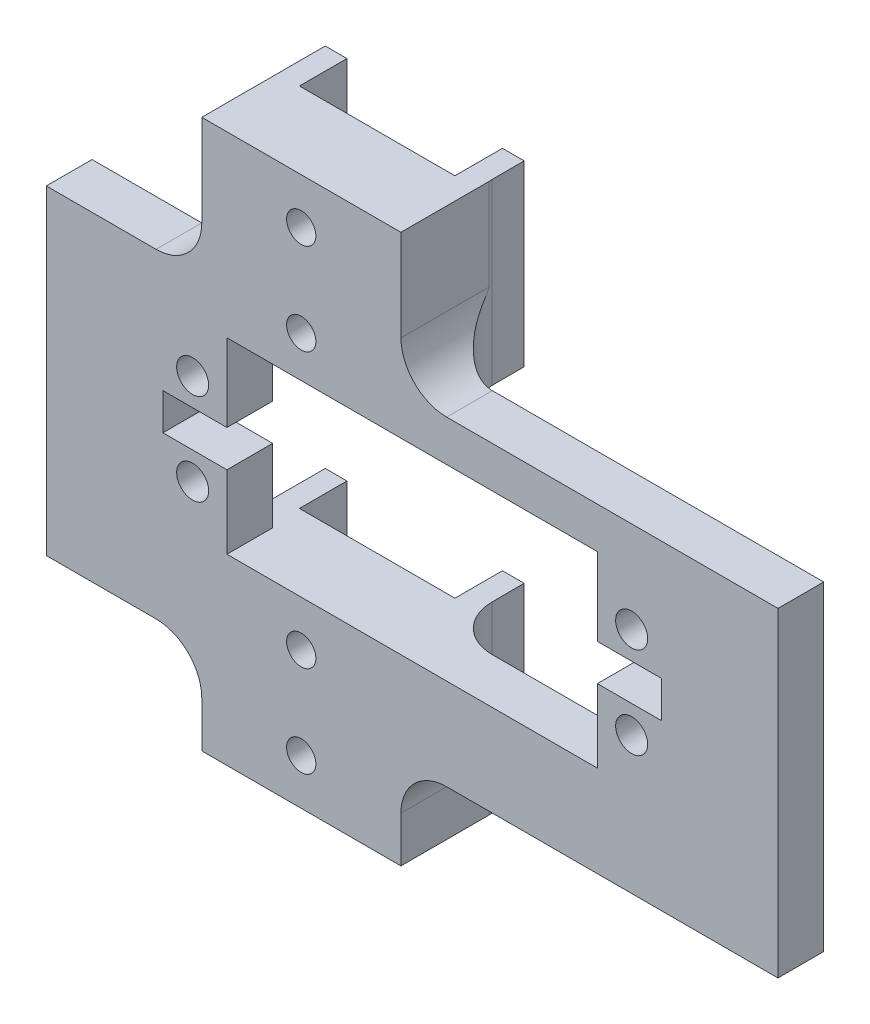
SolidWorks part; units mm, degrees
ref_plane "正面" through (0, 0, 0) normal (0, 0, 1) x (1, 0, 0)
ref_plane "平面" through (0, 0, 0) normal (0, 1, 0) x (1, 0, 0)
ref_plane "右側面" through (0, 0, 0) normal (1, 0, 0) x (0, 0, -1)
sketch "ｽｹｯﾁ1" plane through (0, 0, 0) normal (0, 0, 1) x (1, 0, 0)
  line L0 (-20.25, 10) -> (-20.25, -10)
  line L1 (-24, 5) -> (24, 5) construction
  line L2 (-24, 5) -> (-24, -5) construction
  line L3 (-24, -5) -> (24, -5) construction
  line L4 (24, 5) -> (24, -5) construction
  line L5 (-24, 5) -> (24, -5) construction
  line L6 (-24, -5) -> (24, 5) construction
  line L7 (-29, 10) -> (-20.25, 10)
  line L8 (-29, 10) -> (-29, -20)
  line L9 (-29, -20) -> (29, -20)
  line L10 (29, 10) -> (29, -20)
  line L13 (-20.25, -10) -> (20.25, -10)
  line L14 (20.25, -10) -> (20.25, 10)
  line L16 (0, -12.925) -> (0, 12.925) construction
  line L17 (20.25, 10) -> (29, 10)
  circle A0 centre (-24, 5) radius 1.75
  circle A1 centre (-24, -5) radius 1.75
  circle A2 centre (24, 5) radius 1.75
  circle A3 centre (24, -5) radius 1.75
  point P0 (0, 0)
  point P10 (0, 0)
  dimension "D3" = 3.5
  dimension "D4" = 3.5
  dimension "D5" = 3.5
  dimension "D6" = 3.5
  dimension "D1" = 48
  dimension "D2" = 10
  dimension "D7" = 5
  dimension "D8" = 5
  dimension "D9" = 20.25
  dimension "D10" = 20.25
  dimension "D11" = 20
  dimension "D12" = 30
extrude "ﾎﾞｽ - 押し出し1" add sketch "ｽｹｯﾁ1" along normal blind 5
sketch "ｽｹｯﾁ2" plane through (0, 0, 0) normal (0, 0, -1) x (-1, 0, 0)
  line L0 (20, -10) -> (20, -20)
  line L1 (-20.25, -10) -> (20.25, -10) construction
  line L2 (29, -20) -> (-29, -20) construction
  line L3 (20, -20) -> (23, -20)
  line L4 (23, -20) -> (23, -10)
  line L5 (23, -10) -> (20, -10)
  line L6 (1.25, -10) -> (1.25, -20)
  line L7 (1.25, -20) -> (4.25, -20)
  line L8 (4.25, -20) -> (4.25, -10)
  line L9 (4.25, -10) -> (1.25, -10)
  line L10 (29, 10) -> (29, -20) construction
  dimension "D1" = 6
  dimension "D2" = 3
  dimension "D3" = 3
  dimension "D4" = 15.75
extrude "ﾎﾞｽ - 押し出し2" add sketch "ｽｹｯﾁ2" along normal blind 8.5
sketch "ｽｹｯﾁ3" plane through (0, -10, 0) normal (0, 1, 0) x (1, 0, 0)
  line L0 (-20, 0) -> (-20, 3.3)
  line L1 (-16.5, 0) -> (16.5, 0) construction
  line L2 (-20, 8.5) -> (-20, 0) construction
  line L3 (-20, 3.3) -> (-4.25, 3.3)
  line L4 (-4.25, 8.5) -> (-4.25, 0) construction
  line L5 (-4.25, 3.3) -> (-4.25, 0)
  line L6 (-4.25, 0) -> (-20, 0)
  dimension "D1" = 3.3
extrude "ﾎﾞｽ - 押し出し3" add sketch "ｽｹｯﾁ3" against normal blind 10
sketch "ｽｹｯﾁ4" plane through (0, 0, 0) normal (0, 1, 0) x (1, 0, 0)
  line L0 (-23, 8.5) -> (-23, 0)
  line L1 (-16.5, 0) -> (16.5, 0) construction
  line L2 (-23, 8.5) -> (-23, 0) construction
  line L3 (-23, 0) -> (-1.2236, 0)
  line L4 (-1.2236, 0) -> (-1.25, 8.5)
  line L5 (-1.25, 8.5) -> (-4.25, 8.5)
  line L6 (-4.25, 8.5) -> (-4.25, 3.3)
  line L7 (-4.25, 3.3) -> (-20, 3.3)
  line L8 (-20, 3.3) -> (-20, 8.5)
  line L9 (-20, 8.5) -> (-23, 8.5)
extrude "ﾎﾞｽ - 押し出し4" add sketch "ｽｹｯﾁ4" along normal mid plane 60
sketch "ｽｹｯﾁ6" plane through (0, 0, 0) normal (0, 0, 1) x (1, 0, 0)
  line L0 (-1.2236, -10) -> (-23, -10)
  line L1 (20.25, -10) -> (-20.25, -10) construction
  line L2 (-20.25, -10) -> (-1.2236, -10) construction
  line L3 (-23, -10) -> (-23, 10.5)
  line L4 (-23, 30) -> (-23, 10) construction
  line L5 (-23, 10.5) -> (-1.2236, 10.5)
  line L6 (-1.2236, 30) -> (-1.2236, -10) construction
  line L7 (-1.2236, 10.5) -> (-1.2236, -10)
  dimension "D1" = 20.5
extrude "ｶｯﾄ - 押し出し2" cut sketch "ｽｹｯﾁ6" against normal through all
sketch "ｽｹｯﾁ7" plane through (0, 0, 5) normal (0, 0, 1) x (1, 0, 0)
  line L0 (-29, 10) -> (-29, 15)
  line L1 (-29, 15) -> (29, 15)
  line L2 (29, 15) -> (29, 10)
  line L3 (29, 10) -> (-29, 10)
  dimension "D1" = 5
extrude "ﾎﾞｽ - 押し出し5" add sketch "ｽｹｯﾁ7" against normal blind 5
sketch "ｽｹｯﾁ8" plane through (0, 0, 5) normal (0, 0, 1) x (1, 0, 0)
  line L0 (-20.25, 10) -> (-20.25, 10.5)
  line L1 (-20.25, 10.5) -> (20.25, 10.5)
  line L2 (20.25, 10.5) -> (20.25, 10)
  line L3 (20.25, 10) -> (-20.25, 10)
  dimension "D1" = 0.5
extrude "ｶｯﾄ - 押し出し3" cut sketch "ｽｹｯﾁ8" against normal through all
sketch "ｽｹｯﾁ9" plane through (0, 0, 0) normal (0, 0, 1) x (1, 0, 0)
  line L4 (-23, 15) -> (-1.2236, 15)
  line L8 (-23, 15) -> (-1.2236, 15)
  line L10 (-1.2236, 15) -> (-1.2236, 30)
  line L11 (-1.2236, 15) -> (-1.2236, 30)
  line L16 (-1.2236, -30) -> (-1.2236, -20)
  line L17 (-1.2236, -20) -> (-23, -20)
  line L18 (-23, -20) -> (-23, -30)
  line L19 (-1.2236, -20) -> (-23, -20)
  line L20 (-1.2236, -30) -> (-1.2236, -20)
  line L22 (-23, -20) -> (-23, -30)
  line L24 (-1.2236, 30) -> (-23, 30)
  line L25 (-1.2236, 30) -> (-23, 30)
  line L26 (-23, 30) -> (-23, 15)
  line L27 (-23, 30) -> (-23, 15)
  line L29 (-23, -30) -> (-1.2236, -30)
  line L30 (-23, -30) -> (-1.2236, -30)
  dimension "D1" = 0
  dimension "D2" = 0
extrude "ﾎﾞｽ - 押し出し6" add sketch "ｽｹｯﾁ9" along normal blind 5
fillet "ﾌｨﾚｯﾄ1" radius 5 4 edges at (-23, -20, 2.5) (-1.2236, -20, 2.5) (-1.2236, 15, 2.5) (-23, 15, 2.5)
sketch "ｽｹｯﾁ10" plane through (0, 0, -3.3) normal (0, 0, -1) x (-1, 0, 0)
  line L0 (12.125, 30) -> (12.125, -30) construction
  line L1 (4.25, 30) -> (20, 30) construction
  line L2 (4.25, -30) -> (20, -30) construction
  circle A0 centre (12.125, 25) radius 1.6
  circle A1 centre (12.125, 15) radius 1.6
  circle A2 centre (12.125, -15) radius 1.6
  circle A3 centre (12.125, -25) radius 1.6
  dimension "D1" = 3.2
  dimension "D2" = 3.2
  dimension "D3" = 5
  dimension "D4" = 10
  dimension "D5" = 3.2
  dimension "D6" = 3.2
  dimension "D8" = 10
  dimension "D7" = 5
extrude "ｶｯﾄ - 押し出し4" cut sketch "ｽｹｯﾁ10" against normal through all
fillet "ﾌｨﾚｯﾄ2" radius 5 1 edges at (-1.2236, 15.25, 0)
fillet "ﾌｨﾚｯﾄ3" radius 5 1 edges at (-1.2236, -17.5, 0)
sketch "ｽｹｯﾁ11" plane through (0, 0, 5) normal (0, 0, 1) x (1, 0, 0)
  line L0 (-29, 15) -> (-40, 15)
  line L1 (-40, 15) -> (-40, -20)
  line L2 (-40, -20) -> (-29, -20)
  line L3 (-29, -20) -> (-29, 15)
  line L4 (29, -20) -> (29, 15)
  line L6 (29, 15) -> (40, 15)
  line L7 (40, 15) -> (40, -20)
  line L8 (40, -20) -> (29, -20)
  dimension "D1" = 11
  dimension "D2" = 11
extrude "ﾎﾞｽ - 押し出し7" add sketch "ｽｹｯﾁ11" against normal blind 5
sketch "ｽｹｯﾁ12" plane through (0, -20, 0) normal (0, -1, 0) x (1, 0, 0)
  line L0 (-40, 5) -> (-40, 15)
  line L1 (-40, 15) -> (-30, 15)
  line L2 (-30, 15) -> (-30, 5)
  line L3 (-30, 5) -> (-40, 5)
  line L4 (40, 5) -> (40, 15)
  line L5 (40, 15) -> (30, 15)
  line L6 (30, 15) -> (30, 5)
  line L7 (3.7764, 5) -> (40, 5) construction
  line L8 (30, 5) -> (40, 5)
  dimension "D1" = 10
  dimension "D2" = 10
  dimension "D3" = 10
  dimension "D4" = 10
extrude "ﾎﾞｽ - 押し出し8" add sketch "ｽｹｯﾁ12" against normal blind 5
sketch "ｽｹｯﾁ14" plane through (0, 0, -8.5) normal (0, 0, -1) x (-1, 0, 0)
  line L0 (20, 30) -> (20.625, 30)
  line L1 (20, 30) -> (23, 30) construction
  line L2 (20.625, 30) -> (20.625, -30)
  line L3 (20, -30) -> (23, -30) construction
  line L4 (20.625, -30) -> (20, -30)
  line L5 (20, -30) -> (20, 30)
  line L6 (4.25, 30) -> (3.625, 30)
  line L7 (1.25, 30) -> (4.25, 30) construction
  line L8 (3.625, 30) -> (3.625, 10.5)
  line L9 (1.25, 10.5) -> (4.25, 10.5) construction
  line L11 (4.25, 10.5) -> (4.25, 30)
  line L12 (3.625, 10.5) -> (3.625, -30)
  line L13 (1.25, -30) -> (4.25, -30) construction
  line L14 (3.625, -30) -> (4.25, -30)
  line L15 (4.25, -30) -> (4.25, 10.5)
  dimension "D1" = 0.625
  dimension "D2" = 0.625
extrude "ｶｯﾄ - 押し出し5" cut sketch "ｽｹｯﾁ14" against normal blind 5.2
sketch "ｽｹｯﾁ15" plane through (0, -15, 0) normal (0, 1, 0) x (1, 0, 0)
  line L0 (-40, -5) -> (-40, -15)
  line L1 (-40, -15) -> (-30, -15)
  line L2 (-30, -15) -> (-30, -5)
  line L3 (-30, -5) -> (-40, -5)
  line L4 (30, -5) -> (30, -15)
  line L5 (30, -15) -> (40, -15)
  line L6 (40, -15) -> (40, -5)
  line L7 (40, -5) -> (30, -5)
extrude "ｶｯﾄ - 押し出し6" cut sketch "ｽｹｯﾁ15" against normal blind 10
sketch "ｽｹｯﾁ16" plane through (0, 0, 0) normal (0, 0, -1) x (-1, 0, 0)
  line L0 (20.25, 2) -> (20.25, -2)
  line L1 (20.25, -2) -> (27.25, -2)
  line L2 (27.25, -2) -> (27.25, 2)
  line L3 (27.25, 2) -> (20.25, 2)
  line L4 (-27.25, 2) -> (-27.25, -2)
  line L5 (-27.25, -2) -> (-20.25, -2)
  line L6 (-27.25, 2) -> (-20.25, 2)
  line L7 (-20.25, 2) -> (-20.25, -2)
  line L8 (-20.25, 10.5) -> (-20.25, -10) construction
  line L9 (7.425, 0) -> (-7.425, 0) construction
  line L10 (20.25, -10) -> (20.25, 10.5) construction
  dimension "D1" = 0
  dimension "D2" = 2
  dimension "D3" = 2
  dimension "D4" = 7
  dimension "D5" = 2
  dimension "D6" = 2
  dimension "D7" = 0
  dimension "D8" = 7
extrude "ｶｯﾄ - 押し出し7" cut sketch "ｽｹｯﾁ16" against normal through all both and the other way through all
equation "\"D1@ｽｹｯﾁ14\"=1.25/2"
equation "\"D2@ｽｹｯﾁ14\"=1.25/2"
